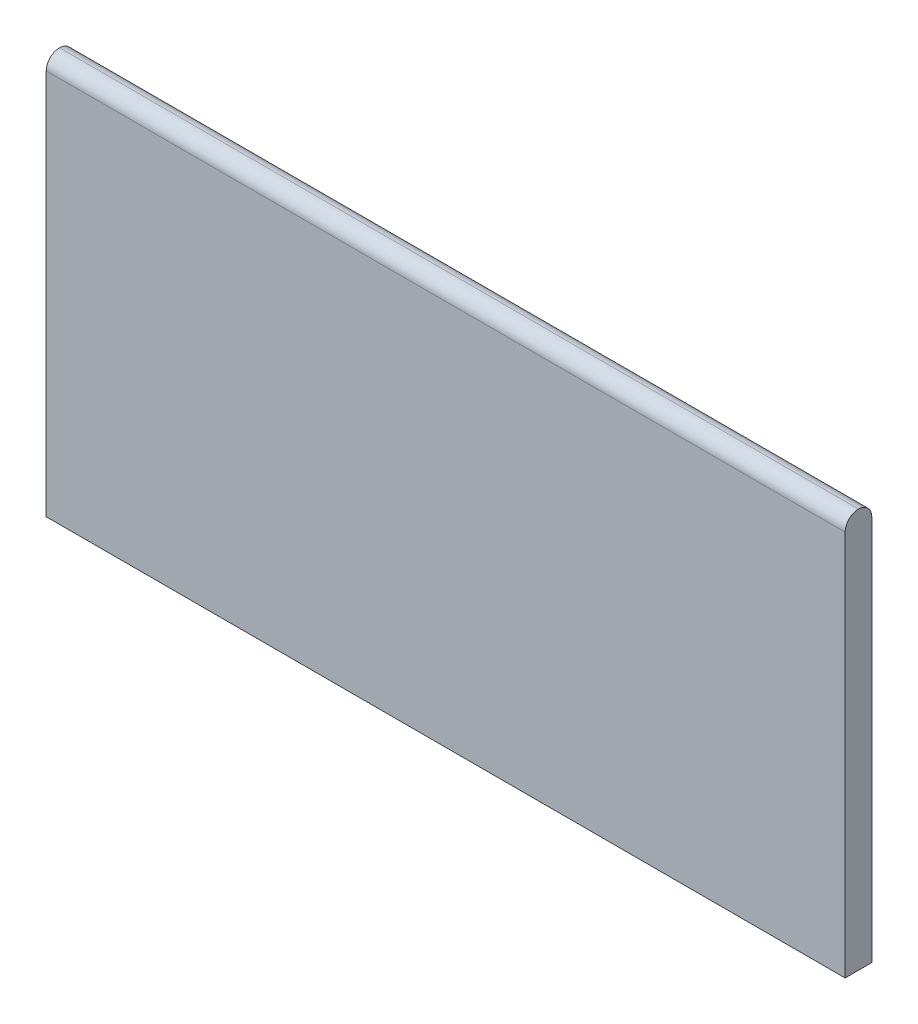
SolidWorks part; units mm, degrees
ref_plane "Front Plane" through (0, 0, 0) normal (0, 0, 1) x (1, 0, 0)
ref_plane "Top Plane" through (0, 0, 0) normal (0, 1, 0) x (1, 0, 0)
ref_plane "Right Plane" through (0, 0, 0) normal (1, 0, 0) x (0, 0, -1)
sketch "Sketch4" plane through (0, 0, 0) normal (0, 0, 1) x (1, 0, 0)
  line L1 (-762, 381) -> (762, 381)
  line L2 (-762, 381) -> (-762, -381)
  line L3 (-762, -381) -> (762, -381)
  line L4 (762, 381) -> (762, -381)
  line L5 (-762, 381) -> (762, -381) construction
  line L6 (-762, -381) -> (762, 381) construction
  point P0 (0, 0)
  dimension "D1" = 1524
  dimension "D2" = 762
extrude "Boss-Extrude1" add sketch "Sketch4" along normal blind 50.8
fillet "Fillet1" radius 25.4 2 edges at (0, 381, 50.8) (0, 381, 0)
